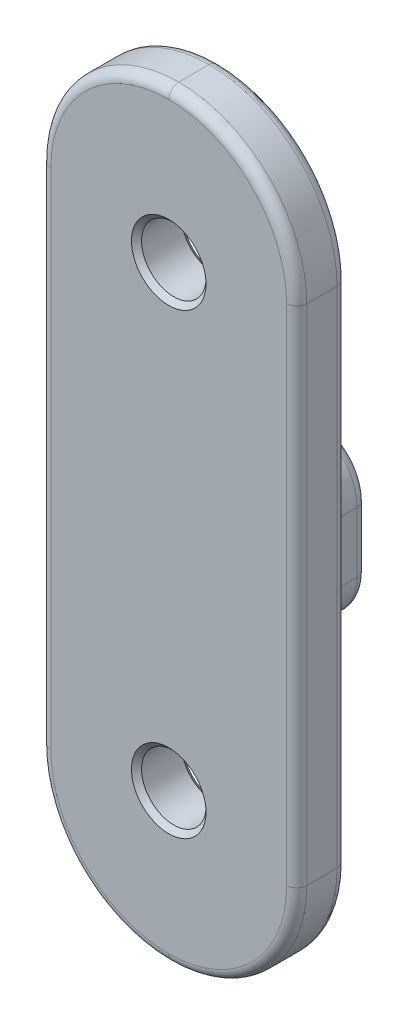
SolidWorks part; units mm, degrees
ref_plane "Front" through (0, 0, 0) normal (0, 0, 1) x (1, 0, 0)
ref_plane "Top" through (0, 0, 0) normal (0, 1, 0) x (1, 0, 0)
ref_plane "Right" through (0, 0, 0) normal (1, 0, 0) x (0, 0, -1)
sketch "Sketch1" plane through (0, 0, 0) normal (0, 0, 1) x (1, 0, 0)
  line L0 (0, 45.4) -> (0, 0) construction
  line L1 (0, 60.4) -> (0, -15) construction
  line L2 (-12.7, 60.4) -> (12.7, 60.4)
  line L3 (-12.7, 60.4) -> (-12.7, -15)
  line L4 (-12.7, -15) -> (12.7, -15)
  line L5 (12.7, 60.4) -> (12.7, -15)
  circle A0 centre (0, 0) radius 3.2
  circle A1 centre (0, 45.4) radius 3.2
  circle A3 centre (0, 45.4) radius 3.2 construction
  circle A5 centre (0, 0) radius 3.2 construction
  point P2 (0, 9.3965)
  point P10 (0, 0)
  point P11 (0, 0)
  point P13 (0.8421, 44.6412)
  point P16 (0, 0.5669)
  dimension "D1" = 6.4
  dimension "D2" = 6.4
  dimension "D5" = 25.4
  dimension "D3" = 45.4
  dimension "D4" = 15
  dimension "D6" = 15
extrude "mainBody" add sketch "Sketch1" along normal blind 5
sketch "Sketch2" plane through (0, 0, 0) normal (0, 0, -1) x (-1, 0, 0)
  line L6 (-12.7, -119.0095) -> (-12.7, 2.7) construction
  line L7 (10.9154, 12.7) -> (9.8493, 12.7) construction
  line L8 (-2.7, 12.7) -> (9.8493, 12.7) construction
  line L9 (8.7602, 32.7) -> (10.3828, 32.7) construction
  line L10 (8.7602, 32.7) -> (-2.7, 32.7) construction
  line L11 (-12.7, 42.7) -> (-12.7, 115.9656) construction
  line L12 (-12.7, -15) -> (-12.7, 60.4) construction
  line L13 (-10.7, 30.7) -> (10.7, 30.7)
  line L14 (-10.7, 30.7) -> (-10.7, 14.7)
  line L15 (-10.7, 14.7) -> (10.7, 14.7)
  line L16 (10.7, 30.7) -> (10.7, 14.7)
  line L17 (12.7, 60.4) -> (12.7, -15) construction
  arc A2 (-2.7, 12.7) -> (-12.7, 2.7) centre (-2.7, 2.7) ccw construction
  arc A3 (-12.7, 42.7) -> (-2.7, 32.7) centre (-2.7, 42.7) ccw construction
  spline S2 degree 3 poles (10.9154, 12.7) (11.3253, 12.7) (11.7124, 12.7475) (12.4403, 12.9461) (12.7577, 13.0912) (13.1717, 13.3645) (13.2975, 13.4639) (13.525, 13.6729) (13.6274, 13.7832) (13.9065, 14.1286) (14.0554, 14.3799) (14.2909, 14.8936) (14.3793, 15.158) (14.5143, 15.6974) (14.5607, 15.9732) (14.6199, 16.5277) (14.6327, 16.8062) (14.6308, 17.2246) (14.6266, 17.3642) (14.6113, 17.6436) (14.6001, 17.7841) (14.5857, 17.9229) knots 0 0 0 0 0.125 0.125 0.25 0.25 0.3125 0.3125 0.375 0.375 0.5 0.5 0.625 0.625 0.75 0.75 0.875 0.875 0.9375 0.9375 1 1 1 1 construction
  spline S3 degree 3 poles (14.0881, 27.9707) (14.091, 28.496) (14.0469, 29.0224) (13.8947, 29.7843) (13.8293, 30.0343) (13.6613, 30.5236) (13.5583, 30.7638) (13.3022, 31.2255) (13.151, 31.4441) (12.877, 31.7473) (12.7778, 31.8442) (12.56, 32.0281) (12.4413, 32.1151) (12.1879, 32.2726) (12.0526, 32.3438) (11.7623, 32.4692) (11.6061, 32.5238) (11.1125, 32.6558) (10.7601, 32.7) (10.3828, 32.7) knots 0 0 0 0 0.25 0.25 0.375 0.375 0.5 0.5 0.625 0.625 0.6875 0.6875 0.75 0.75 0.8125 0.8125 0.875 0.875 1 1 1 1 construction
  point P22 (12.7, 22.7)
  dimension "D1" = 2
  dimension "D2" = 2
  dimension "D3" = 2
  dimension "D4" = 2
extrude "ribSupport" add sketch "Sketch2" along normal blind 4
fillet "Fillet-12.7" radius 12.7 4 edges at (-12.7, -15, 2.5) (12.7, -15, 2.5) (-12.7, 60.4, 2.5) (12.7, 60.4, 2.5)
fillet "Fillet-5.0" radius 5 4 edges at (-10.7, 30.7, -2) (-10.7, 14.7, -2) (10.7, 14.7, -2) (10.7, 30.7, -2)
chamfer "Chamfer-0.5" distance 0.5 angle 45 4 edges at (3.2, 0, 0) (3.2, 0, 5) (3.2, 45.4, 0) (3.2, 45.4, 5)
fillet "Fillet-1.0" radius 1 28 edges at (9.2355, 29.2355, -4) (0, 30.7, -4) (-9.2355, 29.2355, -4) (-10.7, 22.7, -4) (-9.2355, 16.1645, -4) (0, 14.7, -4) (9.2355, 16.1645, -4) (9.2355, 29.2355, 0) (0, 30.7, 0) (-9.2355, 29.2355, 0) (-10.7, 22.7, 0) (-9.2355, 16.1645, 0) (0, 14.7, 0) (9.2355, 16.1645, 0) (8.9803, -11.2803, 0) (-8.9803, -11.2803, 0) (-12.7, 22.7, 0) (-8.9803, 56.6803, 0) (8.9803, 56.6803, 0) (8.9803, -11.2803, 5) (-8.9803, -11.2803, 5) (-12.7, 22.7, 5) (-8.9803, 56.6803, 5) (8.9803, 56.6803, 5) (10.7, 22.7, -4) (10.7, 22.7, 0) (12.7, 22.7, 0) (12.7, 22.7, 5)
equation "\"M6boltHole\"= 6.4"
equation "\"D1@Sketch1\"=\"M6boltHole\""
equation "\"D2@Sketch1\"=\"M6boltHole\""
